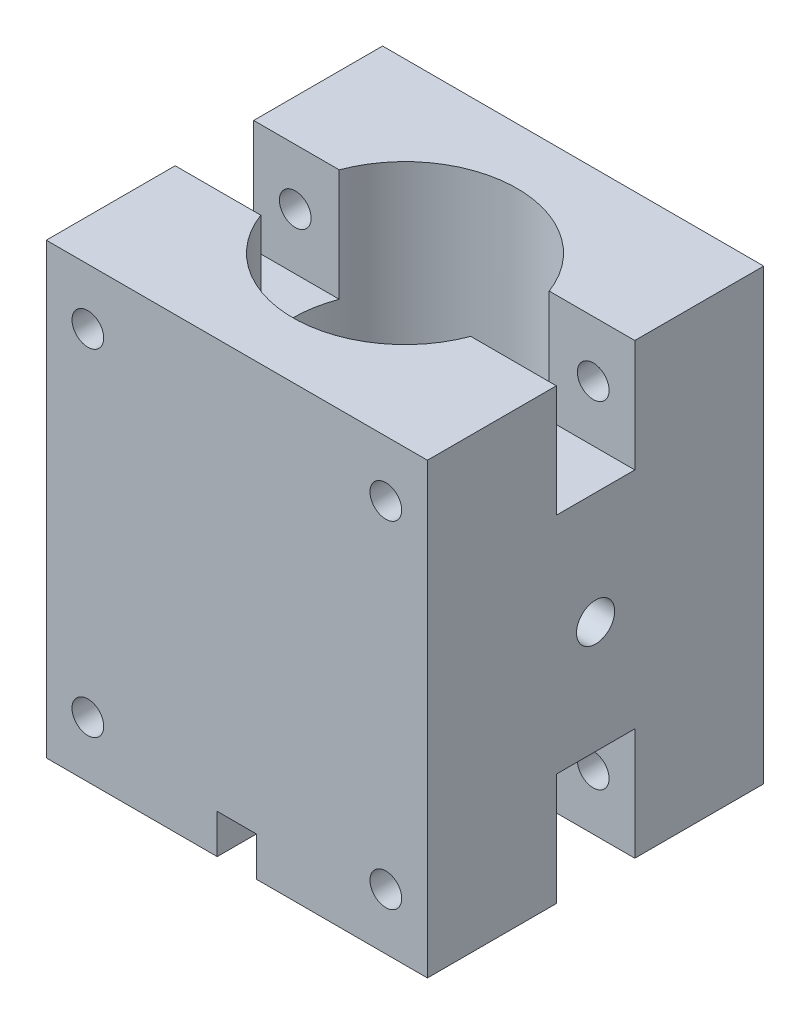
SolidWorks part; units mm, degrees
material "Plain Carbon Steel"
ref_plane "Front Plane" through (0, 0, 0) normal (0, 0, 1) x (1, 0, 0)
ref_plane "Top Plane" through (0, 0, 0) normal (0, 1, 0) x (1, 0, 0)
ref_plane "Right Plane" through (0, 0, 0) normal (1, 0, 0) x (0, 0, -1)
sketch "Sketch1" plane through (0, 0, 0) normal (0, 1, 0) x (1, 0, 0)
  line L0 (0, 0) -> (-20, 0) construction
  line L1 (-19.3649, -5) -> (19.3649, -5) construction
  line L2 (-19.3649, -5) -> (-19.3649, 5) construction
  line L3 (-19.3649, 5) -> (19.3649, 5) construction
  line L4 (19.3649, -5) -> (19.3649, 5) construction
  line L5 (-19.3649, -5) -> (19.3649, 5) construction
  line L6 (-19.3649, 5) -> (19.3649, -5) construction
  line L7 (-20, -30) -> (20, -30) construction
  line L9 (-20, 30) -> (20, 30) construction
  line L10 (20, -30) -> (20, 30) construction
  line L11 (-20, -30) -> (20, 30) construction
  line L12 (-20, 30) -> (20, -30) construction
  line L13 (-20, -30) -> (34, -30)
  line L15 (-20, 30) -> (34, 30)
  line L17 (-35.0062, -25.0044) -> (35, 25) construction
  line L18 (-35.0123, 25.0088) -> (35, -25) construction
  line L21 (-20, 30) -> (-34, 30)
  line L23 (-20, -30) -> (-34, -30)
  line L24 (-34, 30) -> (-34, -30)
  line L31 (34, 30) -> (34, -30)
  circle A2 centre (0, 0) radius 15 construction
  circle A3 centre (0, 0) radius 20
  point P22 (-20, 0)
  dimension "D1" = 30
  dimension "D2" = 40
  dimension "D3" = 10
  dimension "D5" = 40
  dimension "D6" = 60
extrude "Boss-Extrude1" add sketch "Sketch1" along normal mid plane 80
ref_axis "Axis1" through (0, 40, 0) along (0, -1, 0)
sketch "Sketch26" plane through (0, 40, 0) normal (0, 1, 0) x (1, 0, 0)
  line L0 (18.735, 0) -> (-18.735, 0) construction
  line L1 (-18.735, -7) -> (18.735, -7) construction
  line L2 (-18.735, -7) -> (-18.735, 7) construction
  line L3 (-18.735, 7) -> (18.735, 7) construction
  line L4 (18.735, -7) -> (18.735, 7)
  line L5 (-18.735, -7) -> (18.735, 7) construction
  line L6 (-18.735, 7) -> (18.735, -7) construction
  line L7 (0, 7) -> (0, -7) construction
  line L8 (34.435, 0) -> (18.735, 0) construction
  line L9 (34.435, -7) -> (18.735, -7)
  line L10 (34.435, -7) -> (34.435, 7)
  line L11 (34.435, 7) -> (18.735, 7)
  line L12 (18.735, -7) -> (18.735, 7) construction
  line L13 (34.435, -7) -> (18.735, 7) construction
  line L14 (34.435, 7) -> (18.735, -7) construction
  line L15 (-34.435, -7) -> (-18.735, -7)
  line L16 (22.585, -7) -> (30.585, -7) construction
  line L17 (22.585, -7) -> (22.585, 7) construction
  line L18 (22.585, 7) -> (30.585, 7) construction
  line L19 (30.585, -7) -> (30.585, 7) construction
  line L20 (22.585, -7) -> (30.585, 7) construction
  line L21 (22.585, 7) -> (30.585, -7) construction
  line L26 (-18.735, -7) -> (-18.735, 7)
  line L28 (-34.435, -7) -> (-34.435, 7)
  line L29 (-34.435, 7) -> (-18.735, 7)
  circle A1 centre (0, 0) radius 20
  point P0 (0, 0)
  point P10 (26.585, 0)
  point P15 (26.585, 0)
  dimension "D5" = 40
  dimension "D1" = 15.7
  dimension "D2" = 14
  dimension "D3" = 8
  dimension "D4" = 26.585
  dimension "D6" = 18.735
extrude "Cut-Extrude19" cut sketch "Sketch26" against normal blind 20 contours L11 L9 | L10 L11 L9 | L4 | L29 L15 region at (27.0047, 40, 0) region at (19.2424, 40, 0) region at (-27.0047, 40, 0)
sketch "Sketch30" plane through (0, -40, 0) normal (0, -1, 0) x (1, 0, 0)
  line L1 (-46.4697, -7) -> (46.4697, -7)
  line L2 (-46.4697, -7) -> (-46.4697, 7)
  line L3 (-46.4697, 7) -> (46.4697, 7)
  line L4 (46.4697, -7) -> (46.4697, 7)
  line L5 (-46.4697, -7) -> (46.4697, 7) construction
  line L6 (-46.4697, 7) -> (46.4697, -7) construction
  point P0 (0, 0)
  dimension "D1" = 14
extrude "Cut-Extrude22" cut sketch "Sketch30" against normal blind 20
ref_plane "Slide-Center" through (0, 0, 0) normal (1, 0, 0) x (0, 0, -1)
ref_plane "Slide-Center-2" through (0, 0, 0) normal (0, 1, 0) x (1, 0, 0)
ref_plane "Slider-Center-V" through (0, 0, 0) normal (0, 0, 1) x (1, 0, 0)
ref_plane "Slide-Center-3" through (0, 0, 0) normal (0, 0, -1) x (-1, 0, 0)
sketch "Sketch27" plane through (0, 0, 0) normal (0, 0, -1) x (-1, 0, 0)
  line L0 (0, -40) -> (0, 40) construction
  line L1 (-34, -40) -> (34, -40) construction
  line L2 (-34, 40) -> (34, 40) construction
  line L3 (0, -20) -> (0, -40) construction
  line L4 (-34, 20) -> (34, 20) construction
  line L6 (34, 40) -> (34, -40) construction
  line L7 (-34, 30) -> (34, 30) construction
  line L9 (-34, 40) -> (-34, -40) construction
  circle A0 centre (26.58, 30) radius 2.8302
  circle A1 centre (-26.58, 30) radius 2.8302
  dimension "D1" = 20
  dimension "D2" = 10
  dimension "D3" = 26.58
extrude "Cut-Extrude20" cut sketch "Sketch27" against normal up to surface and the other way up to surface up to face at (0, 0, 30) other way up to face at (0, 0, -30)
mirror "Mirror1" about plane through (0, 0, 0) normal (0, 1, 0) of "Cut-Extrude20"
sketch "Sketch33" plane through (-34, 0, 0) normal (-1, 0, 0) x (0, 0, 1)
  circle A0 centre (0, 0) radius 3.4
  dimension "D1" = 6.8
extrude "Cut-Extrude24" cut sketch "Sketch33" against normal blind 20 and the other way blind 30
mirror "Mirror6" about plane through (0, 0, 0) normal (1, 0, 0) of "Cut-Extrude24"
sketch "Sketch37" plane through (0, -40, 0) normal (0, -1, 0) x (1, 0, 0)
  line L1 (-3.5, -35.0089) -> (3.5, -35.0089)
  line L2 (-3.5, -35.0089) -> (-3.5, 35.0089)
  line L3 (-3.5, 35.0089) -> (3.5, 35.0089)
  line L4 (3.5, -35.0089) -> (3.5, 35.0089)
  line L5 (-3.5, -35.0089) -> (3.5, 35.0089) construction
  line L6 (-3.5, 35.0089) -> (3.5, -35.0089) construction
  point P0 (0, 0)
  dimension "D1" = 7
extrude "Cut-Extrude26" cut sketch "Sketch37" against normal blind 7
